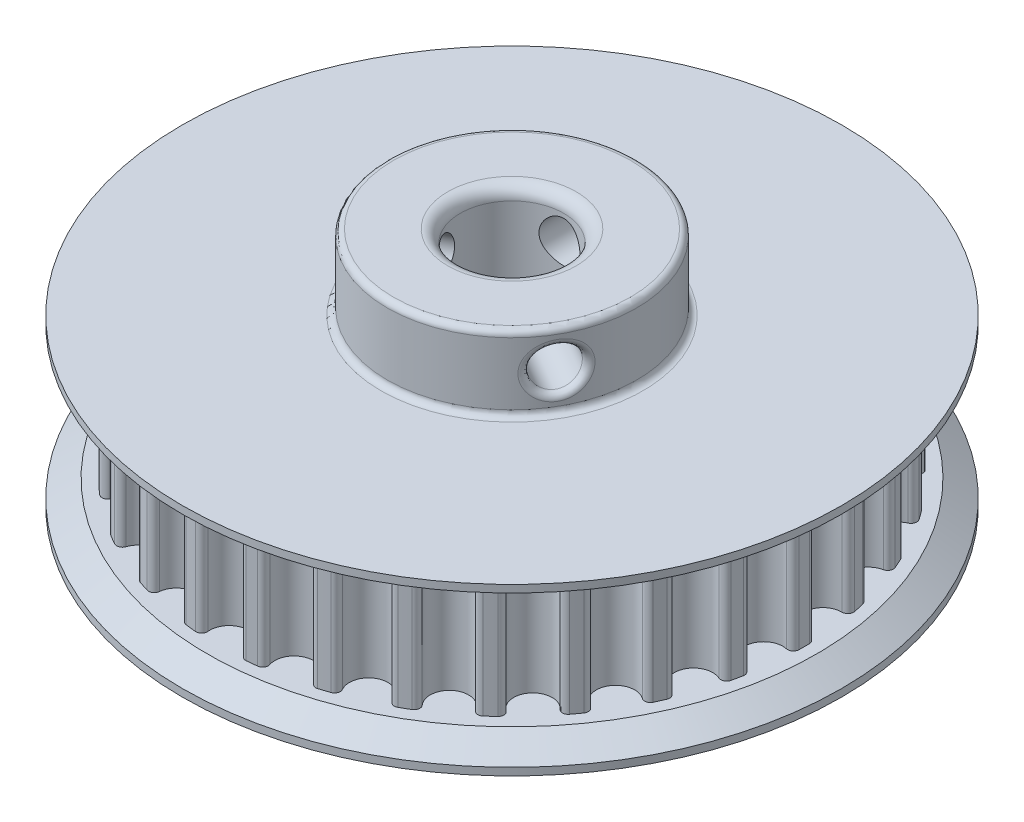
SolidWorks part; units mm, degrees
ref_plane "Plan de face" through (0, 0, 0) normal (0, 0, 1) x (1, 0, 0)
ref_plane "Plan de dessus" through (0, 0, 0) normal (0, 1, 0) x (1, 0, 0)
ref_plane "Plan de droite" through (0, 0, 0) normal (1, 0, 0) x (0, 0, -1)
sketch "Esquisse1" plane through (0, 0, 0) normal (0, 1, 0) x (1, 0, 0)
  line L0 (0, 0) -> (-2.449, 23.3007)
  line L2 (2.449, 23.3007) -> (0, 0)
  line L3 (0, 23.429) -> (0, 0) construction
  line L4 (-2.449, 23.3007) -> (2.449, 23.3007) construction
  circle A1 centre (0, 0) radius 23.429 construction
  arc A2 (-1.5343, 22.836) -> (1.5343, 22.836) centre (0, 22.672) ccw
  arc A3 (-2.449, 23.3007) -> (-2.0293, 23.341) centre (0, 0) cw
  arc A4 (-2.0293, 23.341) -> (-1.5343, 22.836) centre (-1.9897, 22.8847) cw
  arc A5 (2.449, 23.3007) -> (2.0293, 23.341) centre (0, 0) ccw
  arc A6 (2.0293, 23.341) -> (1.5343, 22.836) centre (1.9897, 22.8847) ccw
  arc A7 (-1.5343, 22.836) -> (-1.3662, 23.3892) centre (0, 22.672) cw construction
  arc A8 (1.5343, 22.836) -> (1.3662, 23.3892) centre (0, 22.672) ccw construction
  point P6 (0, 21.129)
  dimension "D2" = 1.543
  dimension "D3" = 0.458
  dimension "D1" = 4.898
  dimension "D4" = 2.3
  dimension "D5" = 12
extrude "Boss.-Extru.1" add sketch "Esquisse1" along normal blind 9.3
pattern_circular "Répétition circulaire1" count 30 over 360 about axis through (0, 9.3, 0) along (0, -1, 0) of "Boss.-Extru.1"
ref_plane "Plan1" through (0, 4.65, 0) normal (0, -1, 0) x (-1, 0, 0)
sketch "Esquisse2" plane through (0, 9.3, 0) normal (0, 1, 0) x (1, 0, 0)
  circle A0 centre (0, 0) radius 26.429
  arc A1 (22.8257, -5.2827) -> (23.001, -4.458) centre (0, 0) ccw construction
  dimension "D1" = 3
extrude "Boss.-Extru.2" add sketch "Esquisse2" along normal blind 2
mirror "Symétrie1" about plane through (0, 4.65, 0) normal (0, -1, 0) of "Boss.-Extru.2"
chamfer "Chanfrein1" distance 2 angle 35 2 edges at (0, 9.3, 26.429) (0, 0, 26.429) first distance on face at (0, 9.3, 0) first distance on face at (0, 0, 0)
sketch "Esquisse4" plane through (0, 11.3, 0) normal (0, 1, 0) x (1, 0, 0)
  circle A0 centre (0, 0) radius 10
  dimension "D1" = 20
extrude "Boss.-Extru.3" add sketch "Esquisse4" along normal blind 6
sketch "Esquisse5" plane through (0, 0, 0) normal (0, 0, 1) x (1, 0, 0)
  line L0 (0, 0) -> (0, 14.3) construction
  line L1 (10, 17.3) -> (-10, 17.3) construction
  circle A0 centre (0, 14.3) radius 1.65
  dimension "D2" = 3.3
  dimension "D1" = 3
extrude "Enlèv. mat.-Extru.2" cut sketch "Esquisse5" against normal through all
pattern_circular "Répétition circulaire2" count 3 over 360 about axis through (0, 17.3, 0) along (0, -1, 0) of "Enlèv. mat.-Extru.2"
sketch "Esquisse3" plane through (0, 17.3, 0) normal (0, 1, 0) x (1, 0, 0)
  circle A0 centre (0, 0) radius 4.15
  dimension "D1" = 8.3
extrude "Enlèv. mat.-Extru.1" cut sketch "Esquisse3" against normal up to next
fillet "Congé1" radius 1 2 edges at (0, -2, -4.15) (0, 17.3, 4.15)
fillet "Congé2" radius 0.5 5 edges at (0, 11.3, 10) (0, 17.3, 10) (0.3544, 12.6885, -9.9937) (-7.7413, 13.9455, 6.3302) (9.3528, 13.9455, 3.5391)
equation "\"nb_tooth\"= 30"
equation "\"D5@Esquisse1\"=360/\"nb_tooth\""
equation "\"D1@Répétition circulaire1\"=\"nb_tooth\""
